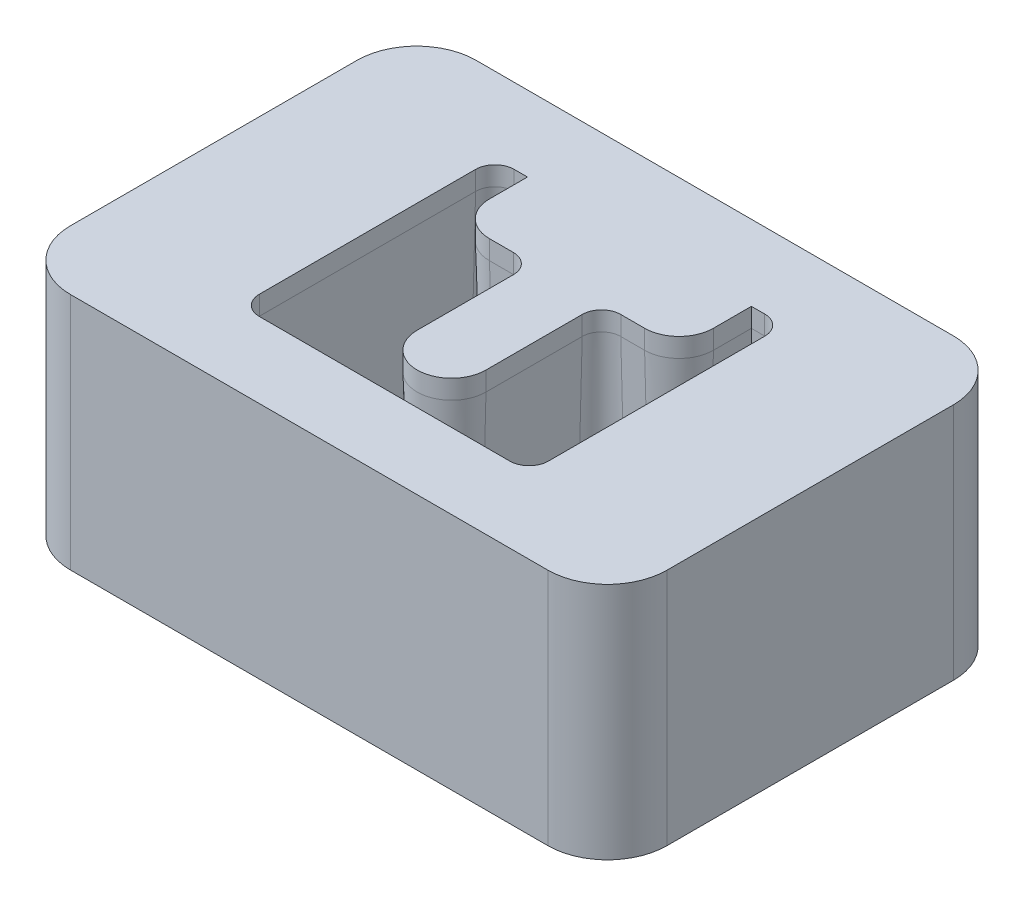
SolidWorks part; units mm, degrees
material "K110"
ref_plane "Front Plane" through (0, 0, 0) normal (0, 0, 1) x (1, 0, 0)
ref_plane "Top Plane" through (0, 0, 0) normal (0, 1, 0) x (1, 0, 0)
ref_plane "Right Plane" through (0, 0, 0) normal (1, 0, 0) x (0, 0, -1)
sketch "Sketch1" plane through (0, 0, 0) normal (0, 1, 0) x (1, 0, 0)
  line L1 (-50, -34) -> (50, -34)
  line L2 (-50, -34) -> (-50, 34)
  line L3 (-50, 34) -> (50, 34)
  line L4 (50, -34) -> (50, 34)
  line L5 (-50, -34) -> (50, 34) construction
  line L6 (-50, 34) -> (50, -34) construction
  point P0 (0, 0)
  dimension "D1" = 68
  dimension "D2" = 100
extrude "Boss-Extrude1" add sketch "Sketch1" against normal blind 40
fillet "Fillet1" radius 10 4 edges at (-50, -20, -34) (50, -20, -34) (50, -20, 34) (-50, -20, 34)
sketch "Sketch2" plane through (0, 0, 0) normal (0, 1, 0) x (1, 0, 0)
  line L22 (-21, -21.36) -> (21, -21.36)
  line L23 (-24.23, 18.13) -> (-24.23, -18.13)
  line L24 (-18.77, 21.36) -> (-21, 21.36)
  line L25 (-18.77, 15) -> (-18.77, 21.36)
  line L26 (-9, 9.23) -> (-13, 9.23)
  line L27 (-5.77, -10.13) -> (-5.77, 6)
  line L28 (5.77, 6) -> (5.77, -10.13)
  line L29 (13, 9.23) -> (9, 9.23)
  line L30 (18.77, 21.36) -> (18.77, 15)
  line L31 (21, 21.36) -> (18.77, 21.36)
  line L32 (24.23, -18.13) -> (24.23, 18.13)
  line L33 (-21, -21.36) -> (21, -21.36)
  line L34 (-24.23, 18.13) -> (-24.23, -18.13)
  line L35 (-18.77, 21.36) -> (-21, 21.36)
  line L36 (-18.77, 15) -> (-18.77, 21.36)
  line L37 (-9, 9.23) -> (-13, 9.23)
  line L38 (-5.77, -10.13) -> (-5.77, 6)
  line L39 (5.77, 6) -> (5.77, -10.13)
  line L40 (13, 9.23) -> (9, 9.23)
  line L41 (18.77, 21.36) -> (18.77, 15)
  line L42 (21, 21.36) -> (18.77, 21.36)
  line L43 (24.23, -18.13) -> (24.23, 18.13)
  arc A18 (21, -21.36) -> (24.23, -18.13) centre (21, -18.13) ccw
  arc A19 (-24.23, -18.13) -> (-21, -21.36) centre (-21, -18.13) ccw
  arc A20 (-21, 21.36) -> (-24.23, 18.13) centre (-21, 18.13) ccw
  arc A21 (-18.77, 15) -> (-13, 9.23) centre (-13, 15) ccw
  arc A22 (-5.77, 6) -> (-9, 9.23) centre (-9, 6) ccw
  arc A23 (-5.77, -10.13) -> (5.77, -10.13) centre (0, -10.13) ccw
  arc A24 (9, 9.23) -> (5.77, 6) centre (9, 6) ccw
  arc A25 (13, 9.23) -> (18.77, 15) centre (13, 15) ccw
  arc A26 (24.23, 18.13) -> (21, 21.36) centre (21, 18.13) ccw
  arc A27 (21, -21.36) -> (24.23, -18.13) centre (21, -18.13) ccw
  arc A28 (-24.23, -18.13) -> (-21, -21.36) centre (-21, -18.13) ccw
  arc A29 (-21, 21.36) -> (-24.23, 18.13) centre (-21, 18.13) ccw
  arc A30 (-18.77, 15) -> (-13, 9.23) centre (-13, 15) ccw
  arc A31 (-5.77, 6) -> (-9, 9.23) centre (-9, 6) ccw
  arc A32 (-5.77, -10.13) -> (5.77, -10.13) centre (0, -10.13) ccw
  arc A33 (9, 9.23) -> (5.77, 6) centre (9, 6) ccw
  arc A34 (13, 9.23) -> (18.77, 15) centre (13, 15) ccw
  arc A35 (24.23, 18.13) -> (21, 21.36) centre (21, 18.13) ccw
  dimension "D1" = 0.23
extrude "Cut-Extrude1" cut sketch "Sketch2" against normal up to next
sketch "Sketch3" plane through (0, 0, 0) normal (0, 0, 1) x (1, 0, 0)
  line L6 (24.23, -3.2) -> (25.1936, -40)
  line L7 (40, -40) -> (40, 0) construction
  line L8 (40, -40) -> (50, -40) construction
  line L11 (37.4, 0) -> (-37.4, 0) construction
  line L12 (25.1936, -40) -> (23.23, -40)
  line L13 (-40, -40) -> (40, -40) construction
  line L14 (23.23, -3.2) -> (24.23, -3.2)
  line L15 (23.23, -40) -> (23.23, -3.2)
  line L16 (24.23, -40) -> (24.23, 0) construction
  dimension "D1" = 3.2
  dimension "D2" = 1.5
  dimension "D3" = 1
sketch "Sketch5" plane through (0, 0, 0) normal (0, 1, 0) x (1, 0, 0)
  line L0 (21, 21.36) -> (18.77, 21.36) construction
  line L1 (24.23, -18.13) -> (24.23, 18.13) construction
  line L2 (18.77, 21.36) -> (18.77, 15) construction
  line L3 (13, 9.23) -> (9, 9.23) construction
  line L4 (5.77, 6) -> (5.77, -10.13) construction
  line L5 (-5.77, -10.13) -> (-5.77, 6) construction
  line L6 (-9, 9.23) -> (-13, 9.23) construction
  line L7 (-18.77, 15) -> (-18.77, 21.36) construction
  line L8 (-18.77, 21.36) -> (-21, 21.36) construction
  line L9 (-24.23, 18.13) -> (-24.23, -18.13) construction
  line L10 (-21, -21.36) -> (21, -21.36) construction
  line L11 (-21, -21.36) -> (21, -21.36)
  line L12 (-24.23, 18.13) -> (-24.23, -18.13)
  line L13 (-18.77, 21.36) -> (-21, 21.36)
  line L14 (-18.77, 15) -> (-18.77, 21.36)
  line L15 (-9, 9.23) -> (-13, 9.23)
  line L16 (-5.77, -10.13) -> (-5.77, 6)
  line L17 (5.77, 6) -> (5.77, -10.13)
  line L18 (13, 9.23) -> (9, 9.23)
  line L19 (18.77, 21.36) -> (18.77, 15)
  line L20 (24.23, -18.13) -> (24.23, 18.13)
  line L21 (21, 21.36) -> (18.77, 21.36)
  arc A0 (-5.77, 6) -> (-9, 9.23) centre (-9, 6) ccw construction
  arc A1 (24.23, 18.13) -> (21, 21.36) centre (21, 18.13) ccw construction
  arc A2 (13, 9.23) -> (18.77, 15) centre (13, 15) ccw construction
  arc A3 (9, 9.23) -> (5.77, 6) centre (9, 6) ccw construction
  arc A4 (-5.77, -10.13) -> (5.77, -10.13) centre (0, -10.13) ccw construction
  arc A5 (-18.77, 15) -> (-13, 9.23) centre (-13, 15) ccw construction
  arc A6 (-21, 21.36) -> (-24.23, 18.13) centre (-21, 18.13) ccw construction
  arc A7 (-24.23, -18.13) -> (-21, -21.36) centre (-21, -18.13) ccw construction
  arc A8 (21, -21.36) -> (24.23, -18.13) centre (21, -18.13) ccw construction
  arc A9 (21, -21.36) -> (24.23, -18.13) centre (21, -18.13) ccw
  arc A10 (-24.23, -18.13) -> (-21, -21.36) centre (-21, -18.13) ccw
  arc A11 (-21, 21.36) -> (-24.23, 18.13) centre (-21, 18.13) ccw
  arc A12 (-18.77, 15) -> (-13, 9.23) centre (-13, 15) ccw
  arc A13 (-5.77, 6) -> (-9, 9.23) centre (-9, 6) ccw
  arc A14 (-5.77, -10.13) -> (5.77, -10.13) centre (0, -10.13) ccw
  arc A15 (9, 9.23) -> (5.77, 6) centre (9, 6) ccw
  arc A16 (13, 9.23) -> (18.77, 15) centre (13, 15) ccw
  arc A17 (24.23, 18.13) -> (21, 21.36) centre (21, 18.13) ccw
sweep "Cut-Sweep1" cut profiles "Sketch3" path "Sketch5"
hole_wizard "M6 Tapped Hole1" positions "Sketch11" profile "Sketch9" tap size "M6" standard "ISO"
sketch "Sketch11" plane through (0, -40, 0) normal (0, -1, 0) x (-1, 0, 0)
  line L0 (-40, 34) -> (40, 34) construction
  line L1 (-50, -24) -> (-50, 24) construction
  line L2 (50, 24) -> (50, -24) construction
  line L3 (40, -34) -> (-40, -34) construction
  point P0 (-43, 27)
  point P2 (43, 27)
  point P4 (43, -27)
  point P6 (-43, -27)
  dimension "D1" = 7
  dimension "D2" = 7
  dimension "D3" = 7
  dimension "D4" = 7
sketch "Sketch9" plane through (43, -40, -27) normal (1, 0, 0) x (0, 0, -1)
  line L0 (0, 0) -> (0, 18.5022)
  line L1 (0, 18.5022) -> (2.5, 17)
  line L2 (2.5, 17) -> (2.5, 0.525)
  line L3 (2.5, 0.525) -> (3.025, 0)
  line L5 (3.025, 0) -> (0, 0)
  line L6 (-2.5, 0.525) -> (-3.025, 0) construction
  line L10 (0, 18.5022) -> (-2.5, 17) construction
  line L11 (0, -6.35) -> (0, 107.95) construction
  dimension "Tap Drill Dia." = 5
  dimension "Tap Drill Depth" = 17
  dimension "Near C'Sink Dia." = 6.05
  dimension "Near C'Sink Angle" = 90
  dimension "Drill Angle" = 118
cosmetic thread "Hole Thread1"
cosmetic thread "Hole Thread2"
cosmetic thread "Hole Thread3"
cosmetic thread "Hole Thread4"
